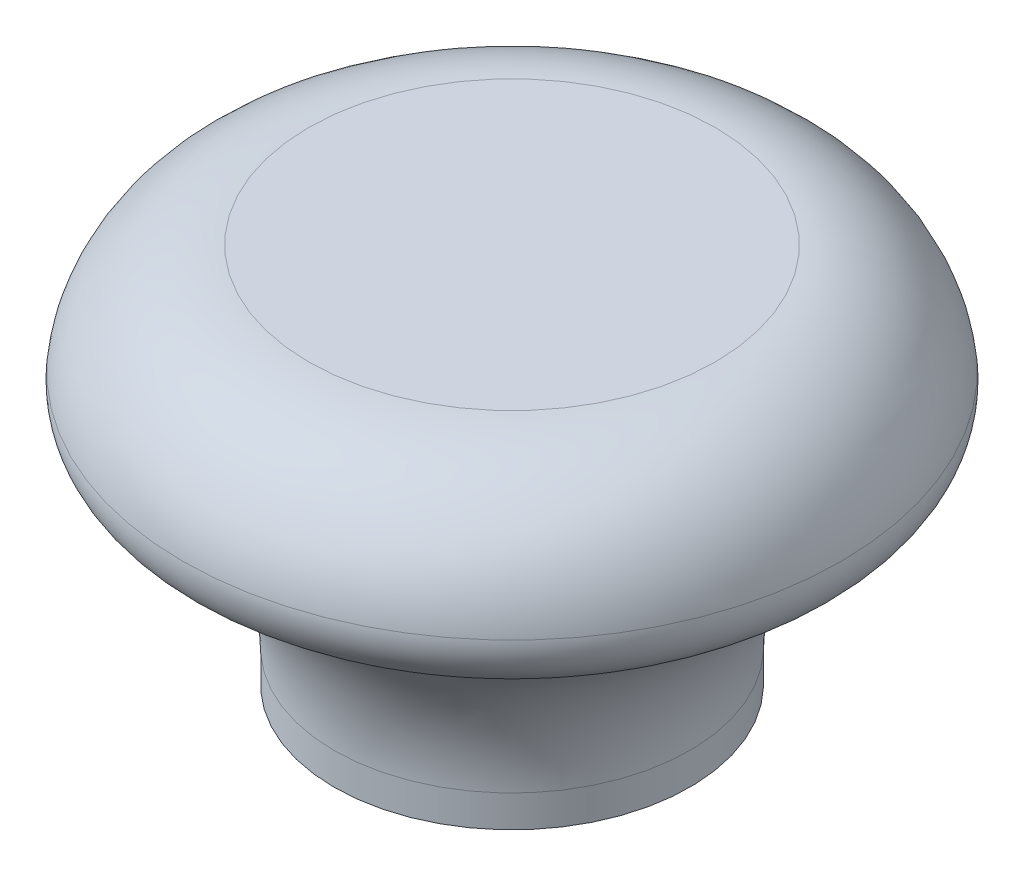
SolidWorks part; units mm, degrees
ref_plane "前视基准面" through (0, 0, 0) normal (0, 0, 1) x (1, 0, 0)
ref_plane "上视基准面" through (0, 0, 0) normal (0, 1, 0) x (1, 0, 0)
ref_plane "右视基准面" through (0, 0, 0) normal (1, 0, 0) x (0, 0, -1)
sketch "草图1" plane through (0, 0, 0) normal (0, 1, 0) x (1, 0, 0)
  circle A0 centre (0, 0) radius 3.5
  dimension "D1" = 7
extrude "凸台-拉伸1" add sketch "草图1" along normal blind 4.5
sketch "草图2" plane through (0, 4.5, 0) normal (0, 1, 0) x (1, 0, 0)
  circle A0 centre (0, 0) radius 6.5
  dimension "D1" = 13
extrude "凸台-拉伸2" add sketch "草图2" along normal blind 3
fillet "圆角1" radius 2.5 1 edges at (0, 7.5, 6.5)
fillet "圆角2" radius 4 1 edges at (0, 4.5, 3.5)
sketch "草图3" plane through (0, 0, 0) normal (0, -1, 0) x (1, 0, 0)
  line L1 (-1.625, -1.4078) -> (1.625, -1.4078)
  line L2 (-1.625, -1.4078) -> (-1.625, 1.4078)
  line L3 (-1.625, 1.4078) -> (1.625, 1.4078)
  line L4 (1.625, -1.4078) -> (1.625, 1.4078)
  line L5 (-1.625, -1.4078) -> (1.625, 1.4078) construction
  line L6 (-1.625, 1.4078) -> (1.625, -1.4078) construction
  circle A0 centre (0, 0) radius 2.15
  dimension "D1" = 4.3
  dimension "D2" = 3.25
extrude "切除-拉伸1" cut sketch "草图3" against normal blind 6.5 contours L3 A0 | L1 L4 L3 L2 | L1 A0 region at (0, 0, 0) region at (0, 0, -1.7096) region at (0, 0, 1.7096)
fillet "圆角3" radius 1 1 edges at (0, 4.5, 6.5)
